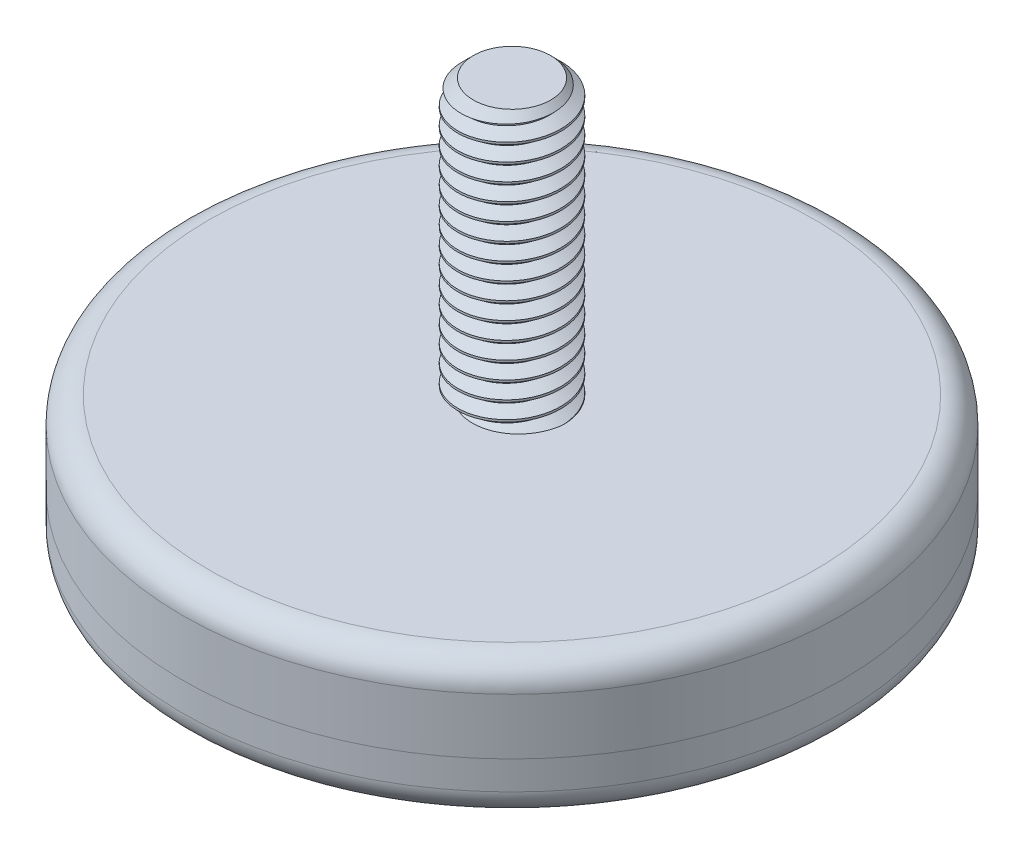
SolidWorks part; units mm, degrees
note: The reader was unsure of these and kept them because the rebuilt part matched: shared geometry of "Sketch8<3>".
ref_plane "Front" through (0, 0, 0) normal (0, 0, 1) x (1, 0, 0)
ref_plane "Top" through (0, 0, 0) normal (0, 1, 0) x (1, 0, 0)
ref_plane "Right" through (0, 0, 0) normal (1, 0, 0) x (0, 0, -1)
sketch "Sketch1" plane through (0, 0, 0) normal (0, 0, 1) x (1, 0, 0)
  line L0 (0, 0) -> (0, 38.1)
  line L1 (-30.48, 0) -> (30.48, 0) construction
  line L2 (-4.7625, 38.1) -> (4.7625, 38.1) construction
  line L3 (30.48, 0) -> (30.48, 12.7) construction
  line L4 (30.48, 12.7) -> (-30.48, 12.7) construction
  line L5 (-30.48, 12.7) -> (-30.48, 0) construction
  line L6 (4.7625, 38.1) -> (4.7625, 12.7) construction
  line L7 (4.7625, 38.1) -> (4.7625, 0)
  line L8 (4.7625, 0) -> (0, 0)
  line L9 (0, 38.1) -> (4.7625, 38.1)
  line L10 (0, 12.7) -> (-4.7625, 12.7) construction
  point P9 (0, 12.7)
  dimension "D1" = 12.7
revolve "Revolve1" add sketch "Sketch1" angle 360 mid plane about L0
sketch "Sketch2" plane through (0, 38.1, 0) normal (0, 1, 0) x (1, 0, 0)
  circle A1 centre (0, 0) radius 4.7625
  circle A2 centre (0, 0) radius 4.7625
  dimension "D1" = 0
curve "Helix/Spiral1" pitch 1.5875 height 38.1 turns 24 parameters "Thread Pitch"=1.5875
sketch "Sketch4" plane through (0, 0, 0) normal (0, 0, 1) x (1, 0, 0)
  line L0 (4.7625, 38.1) -> (3.7314, 38.6953)
  line L1 (3.7314, 38.6953) -> (3.7314, 38.8938)
  line L2 (3.7314, 38.8938) -> (4.7625, 39.4891)
  line L3 (4.7625, 39.4891) -> (4.7625, 38.1)
  line L4 (3.7314, 38.7945) -> (4.7625, 38.7945) construction
  line L5 (4.2469, 38.3977) -> (4.2469, 39.1914) construction
  line L6 (4.7625, 38.1) -> (4.7625, 36.5125) construction
  line L7 (4.7625, 36.5125) -> (4.7625, 34.925) construction
  line L8 (4.7625, 34.925) -> (4.7625, 33.3375) construction
  line L9 (4.7625, 33.3375) -> (4.7625, 31.75) construction
  line L10 (4.7625, 31.75) -> (4.7625, 30.1625) construction
  dimension "D1" = 60
  dimension "D2" = 0.1984
  dimension "D3" = 0.7937
  dimension "D4" = 1.0311
  dimension "D5" = 1.5875
sweep "Cut-Sweep4" cut profiles "Sketch4" path "Helix/Spiral1" align with end faces yes
sketch "Sketch9" plane through (0, 0, 0) normal (0, 0, 1) x (1, 0, 0)
  line L0 (4.7625, 36.9094) -> (3.5719, 38.1)
  line L1 (4.7625, 38.1) -> (4.7625, 0) construction
  line L2 (3.5719, 38.1) -> (4.7625, 38.1)
  line L3 (4.7625, 38.1) -> (4.7625, 36.9094)
  dimension "D1" = 1.1906
revolve "Cut-Revolve2" cut sketch "Sketch9" angle 360 mid plane about L0
sketch "Sketch5" plane through (0, 0, 0) normal (1, 0, 0) x (0, 0, -1)
  line L0 (-4.7625, 0) -> (4.7625, 0) construction
  line L1 (-5.9206, 0) -> (-3.6044, 0)
  line L2 (3.6044, 0) -> (3.6044, 12.7)
  line L3 (3.6044, 12.7) -> (5.9206, 12.7)
  line L4 (5.9206, 12.7) -> (5.9206, 0)
  line L5 (5.9206, 0) -> (3.6044, 0)
  line L6 (-3.6044, 0) -> (-3.6044, 12.7)
  line L7 (-3.6044, 12.7) -> (-5.9206, 12.7)
  line L8 (-5.9206, 12.7) -> (-5.9206, 0)
  dimension "D1" = 9.525
  dimension "D2" = 1.1581
extrude "Cut-Extrude1" cut sketch "Sketch5" against normal through all and the other way through all
sketch "Sketch6" plane through (0, 0, 0) normal (0, 0, 1) x (1, 0, 0)
  line L0 (0, 5.08) -> (30.48, 5.08)
  line L1 (30.48, 0) -> (30.48, 5.08) construction
  line L2 (30.48, 5.08) -> (30.48, 12.7)
  line L3 (30.48, 12.7) -> (0, 12.7)
  line L4 (30.48, 12.7) -> (-30.48, 12.7) construction
  line L5 (0, 12.7) -> (0, 5.08)
  dimension "D1" = 5.08
revolve "Revolve2" add sketch "Sketch6" angle 360 mid plane about L0
fillet "Fillet1" radius 2.4384 1 edges at (30.48, 12.7, 0)
sketch "Sketch8" plane through (0, 0, 0) normal (0, 0, 1) x (1, 0, 0)
  line L0 (0, 0) -> (0, 5.08)
  line L1 (-30.48, 5.08) -> (30.48, 5.08) construction
  line L2 (0, 5.08) -> (30.48, 5.08)
  line L3 (30.48, 5.08) -> (30.48, 0)
  line L4 (30.48, 0) -> (0, 0)
revolve "Revolve3" add sketch "Sketch8" angle 360 mid plane about L0
revolve "Cut-Revolve1" cut sketch "Sketch8<3>" angle 360 mid plane about L0
sketch "Sketch8<3>" plane through (0, 0, 0) normal (0, 0, 1) x (1, 0, 0) same geometry as "Sketch8"
fillet "Fillet2" radius 2.4384 1 edges at (30.48, 0, 0)
sketch "Sketch7" [suppressed] plane through (0, 0, 0) normal (1, 0, 0) x (0, 0, -1)
  line L0 (-11.3018, 0) -> (-11.3018, 26.9875) construction
  line L1 (-11.3018, 26.9875) -> (-6.35, 26.9875)
  line L2 (-6.35, 26.9875) -> (-6.35, 0) construction
  line L3 (-6.35, 0) -> (-11.3018, 0) construction
  line L4 (-6.35, 0) -> (6.35, 0) construction
  line L5 (6.35, 0) -> (11.3018, 0) construction
  line L6 (11.3018, 0) -> (11.3018, 26.9875) construction
  line L7 (11.3018, 26.9875) -> (6.35, 26.9875)
  line L8 (6.35, 26.9875) -> (6.35, 0) construction
  line L9 (-11.3018, 26.9875) -> (-11.3018, 12.7)
  line L10 (32.7152, 12.7) -> (-32.7152, 12.7) construction
  line L11 (-11.3018, 12.7) -> (-6.35, 12.7)
  line L12 (-6.35, 12.7) -> (-6.35, 26.9875)
  line L13 (11.3018, 26.9875) -> (11.3018, 12.7)
  line L14 (11.3018, 12.7) -> (6.35, 12.7)
  line L15 (7.7482, 12.7) -> (0, 12.7) construction
  line L16 (6.35, 12.7) -> (6.35, 26.9875)
  dimension "D1" = 12.7
extrude "Cut-Extrude2" [suppressed] cut sketch "Sketch7" against normal through all and the other way through all
equation "\"D3@Helix/Spiral1\" = \"Overall Ht@Sketch1\""
equation "\"D2@Sketch4\" = \"Thread Pitch@Helix/Spiral1\" * .125"
equation "\"D3@Sketch4\" = \"Thread Pitch@Helix/Spiral1\" * .5"
equation "\"D1@Sketch5\" = \"Thread Major Dia@Sketch1\""
equation "\"D2@Sketch5\" = \"D4@Sketch4\" + .005"
equation "\"D1@Fillet1\" = \"Base Dia@Sketch1\" * .04"
equation "\"D1@Sketch6\" = \"D1@Sketch1\" * .4"
equation "\"D1@Fillet2\" = \"D1@Fillet1\""
equation "\"D5@Sketch4\" = \"Thread Pitch@Helix/Spiral1\""
equation "\"D1@Sketch9\" = \"Thread Pitch@Helix/Spiral1\" * .75"
